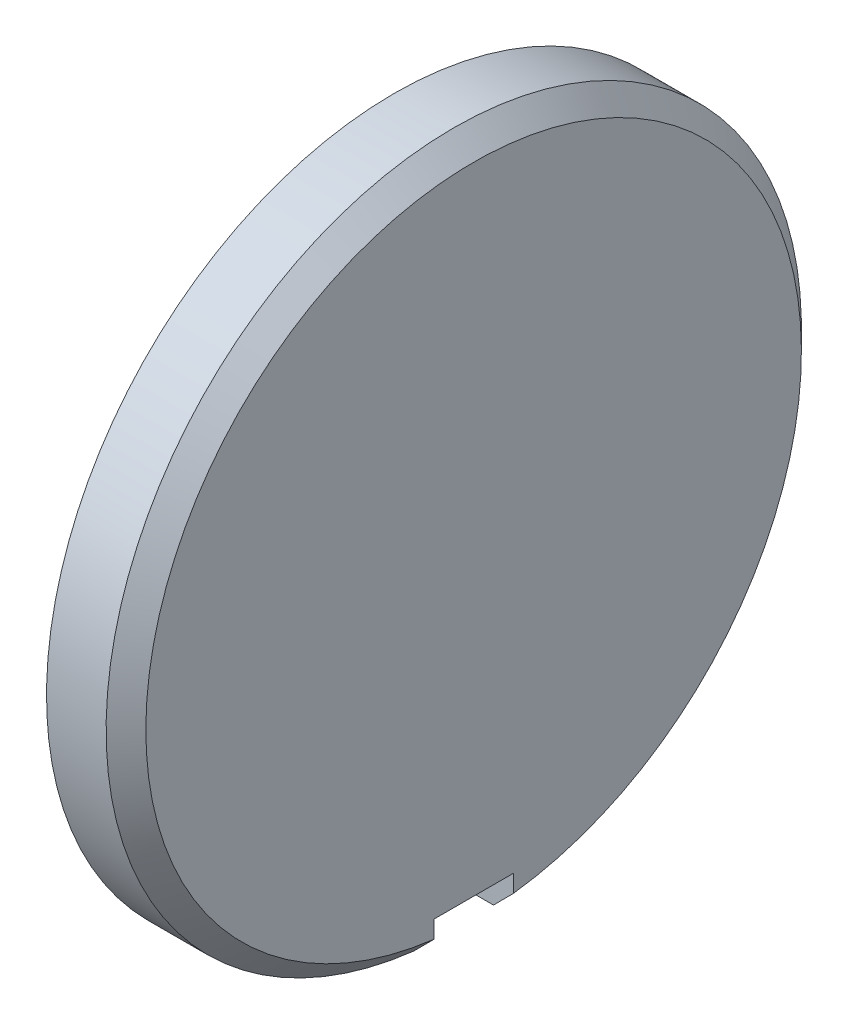
SolidWorks part; units mm, degrees
ref_plane "Front Plane" through (0, 0, 0) normal (0, 0, 1) x (1, 0, 0)
ref_plane "Top Plane" through (0, 0, 0) normal (0, 1, 0) x (1, 0, 0)
ref_plane "Right Plane" through (0, 0, 0) normal (1, 0, 0) x (0, 0, -1)
ref_plane "Plane1" through (0, 0, 66) normal (0, 0, 1) x (1, 0, 0)
sketch "Sketch1" plane through (0, 0, 66) normal (0, 0, 1) x (1, 0, 0)
  line L0 (77.8, -65) -> (90.6, -65) construction
  line L1 (82.8, -62.7) -> (84, -62.7)
  line L2 (84, -62.7) -> (84, -65)
  line L3 (84, -65) -> (85.6, -65)
  line L4 (85.6, -65) -> (85.6, -58.4)
  line L5 (85.6, -58.4) -> (85.2, -58)
  line L6 (85.2, -58) -> (84, -58)
  line L7 (84, -58) -> (84, -62)
  line L8 (84, -62) -> (82.8, -62)
  line L9 (82.8, -62) -> (82.8, -62.7)
revolve "Revolve1" add sketch "Sketch1" angle 360 about L0
sketch "Sketch2" plane through (0, 0, 0) normal (0, 0, 1) x (1, 0, 0)
  line L1 (82.7, -65.4) -> (83.98, -65.4)
  line L2 (82.7, -65.4) -> (82.7, -64.6)
  line L3 (82.7, -64.6) -> (83.98, -64.6)
  line L4 (83.98, -65.4) -> (83.98, -64.6)
extrude "Boss-Extrude1" add sketch "Sketch2" along normal blind 6.4 from offset 62.8 separate body
combine bodies "Combine1" operation type subtract main body 101 bodies to subtract 102
sketch "Sketch3" plane through (0, 0, 0) normal (0, 0, 1) x (1, 0, 0)
  line L1 (82.7, -68.2) -> (83.98, -68.2)
  line L2 (82.7, -68.2) -> (82.7, -61.8)
  line L3 (82.7, -61.8) -> (83.98, -61.8)
  line L4 (83.98, -68.2) -> (83.98, -61.8)
extrude "Boss-Extrude2" add sketch "Sketch3" along normal blind 0.8 from offset 65.6 separate body
combine bodies "Combine2" operation type subtract main body 103 bodies to subtract 104
sketch "Sketch4" plane through (0, 0, 0) normal (0, 0, 1) x (1, 0, 0)
  line L1 (83.9, -72.1) -> (85.7, -72.1)
  line L2 (83.9, -72.1) -> (83.9, -71.2)
  line L3 (83.9, -71.2) -> (85.7, -71.2)
  line L4 (85.7, -72.1) -> (85.7, -71.2)
extrude "Boss-Extrude3" add sketch "Sketch4" along normal blind 1.6 from offset 65.2 separate body
combine bodies "Combine3" operation type subtract main body 105 bodies to subtract 106
